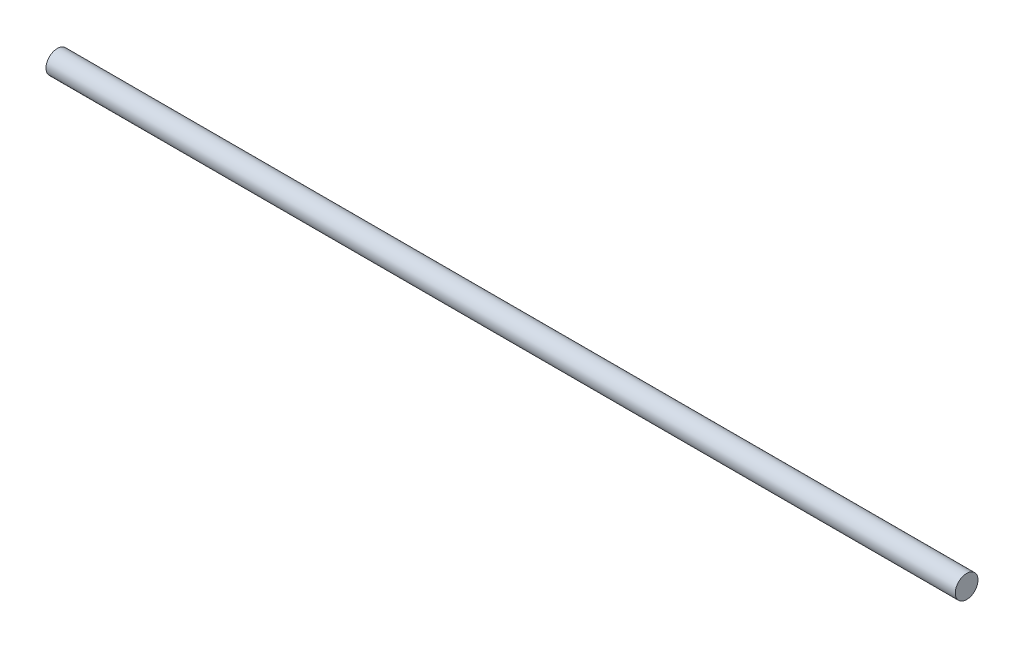
SolidWorks part; units mm, degrees
ref_plane "Front Plane" through (0, 0, 0) normal (0, 0, 1) x (1, 0, 0)
ref_plane "Top Plane" through (0, 0, 0) normal (0, 1, 0) x (1, 0, 0)
ref_plane "Right Plane" through (0, 0, 0) normal (1, 0, 0) x (0, 0, -1)
sketch "Sketch1" plane through (0, 0, 0) normal (1, 0, 0) x (0, 0, -1)
  circle A0 centre (0, 0) radius 2.5
  dimension "D1" = 5
extrude "Boss-Extrude1" add sketch "Sketch1" along normal blind 200
